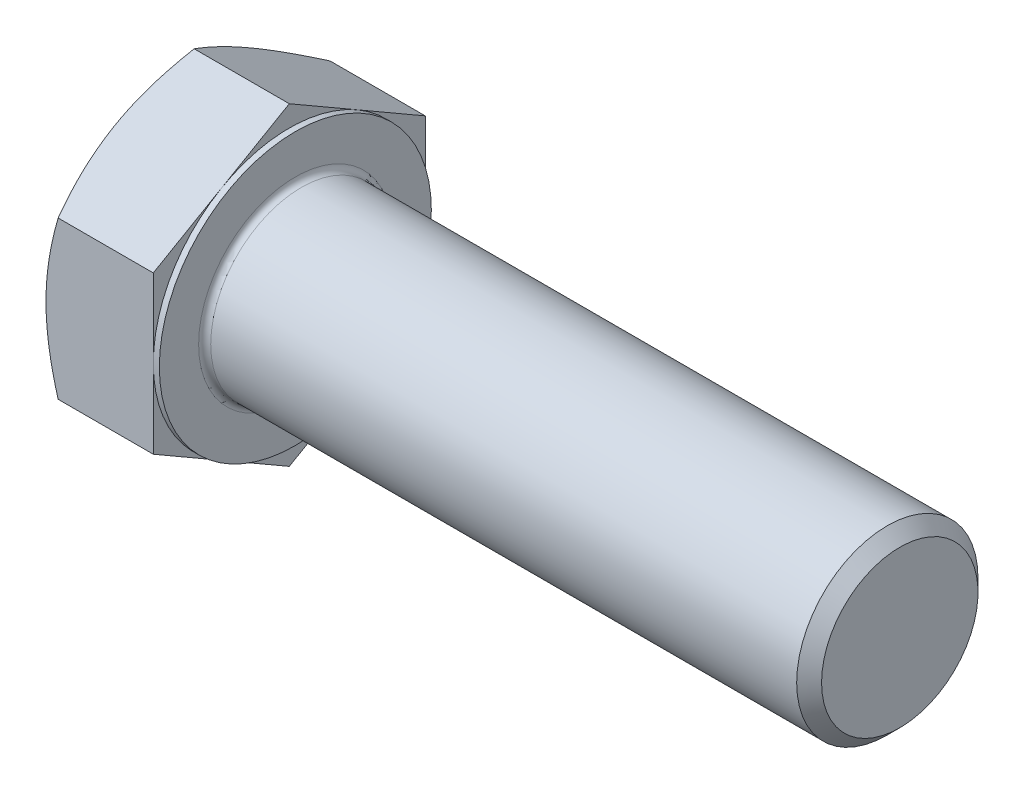
SolidWorks part; units mm, degrees
ref_plane "Front Plane" through (0, 0, 0) normal (0, 0, 1) x (1, 0, 0)
ref_plane "Top Plane" through (0, 0, 0) normal (0, 1, 0) x (1, 0, 0)
ref_plane "Right Plane" through (0, 0, 0) normal (1, 0, 0) x (0, 0, -1)
sketch "BaseHeadSke" plane through (0, 0, 0) normal (1, 0, 0) x (0, 0, -1)
  line L1 (18, 10.3923) -> (0, 20.7846)
  line L2 (0, 20.7846) -> (-18, 10.3923)
  line L3 (-18, 10.3923) -> (-18, -10.3923)
  line L4 (-18, -10.3923) -> (0, -20.7846)
  line L5 (0, -20.7846) -> (18, -10.3923)
  line L6 (18, -10.3923) -> (18, 10.3923)
  circle A0 centre (0, 0) radius 18 construction
extrude "BaseHead" add sketch "BaseHeadSke" along normal blind 15
sketch "BodySke" plane through (0, 0, 0) normal (0, 0, 1) x (1, 0, 0)
  line L0 (0, 0) -> (95, 0)
  line L1 (95, 0) -> (95, 10.352)
  line L2 (95, 10.352) -> (93.352, 12)
  line L3 (93.352, 12) -> (0, 12)
  line L4 (0, 12) -> (0, 0)
  line L5 (15, 10.3923) -> (15, -10.3923) construction
  line L6 (0, 0) -> (159.3976, 0) construction
  line L7 (15, -84.3176) -> (15, 77.7215) construction
  line L8 (92, -21.5941) -> (92, 39.2994) construction
  dimension "Thread_length" = 80
  dimension "Advance" = 3
revolve "BaseBody" add sketch "BodySke" angle 360 about L6
cosmetic thread "ThreadCosmetic" [suppressed] parameters "Thread_length"=80, "Thread_minor"=20.704
sketch "HeadChamferSke" plane through (0, 0, 0) normal (0, 0, 1) x (1, 0, 0)
  line L0 (1.6077, 20.7846) -> (0, 20.7846)
  line L1 (0, 20.7846) -> (0, 18)
  line L2 (0, 18) -> (1.6077, 20.7846)
  line L3 (0, 0) -> (120.9185, 0) construction
  dimension "D1" = 30
revolve "HeadChamfer" cut sketch "HeadChamferSke" angle 360 about L3
sketch "BearingFaceSke" plane through (0, 0, 0) normal (0, 0, 1) x (1, 0, 0)
  line L0 (0, 0) -> (129.6443, 0) construction
  line L1 (14.2, 20.7846) -> (15, 20.7846)
  line L2 (14.2, 20.7846) -> (14.2, 18)
  line L3 (14.2, 18) -> (15, 18)
  line L4 (15, 20.7846) -> (15, 18)
  dimension "D1" = 36
revolve "BearingFace" cut sketch "BearingFaceSke" angle 360 about L0
fillet "Fillet" radius 0.8 1 edges at (15, 0, 12)
sketch "ThdSchSke" plane through (0, 0, 0) normal (0, 0, 1) x (1, 0, 0)
  line L0 (91.0485, 13.9029) -> (91.0485, 12)
  line L1 (91.0485, 12) -> (92, 10.352)
  line L2 (92, 10.352) -> (92.9515, 12)
  line L3 (92.9515, 12) -> (92.9515, 13.9029)
  line L4 (92.9515, 13.9029) -> (91.0485, 13.9029)
  line L6 (0, 0) -> (141.9934, 0) construction
  line L7 (95, -10.352) -> (95, 10.352) construction
  dimension "D2" = 20.704
  dimension "D3" = 24
  dimension "Advance" = 3
revolve "ThreadSchematic" [suppressed] cut sketch "ThdSchSke" angle 360 about L6
pattern_linear "ThdSchPat" [suppressed] count 25 spacing 3 along (-1, 0, 0) of bodies 107
equation "\"Thread_minor@ThreadCosmetic\" = \"Minor_dia@BodySke\""
equation "\"Thread_length@ThreadCosmetic\" = \"Thread_length@BodySke\""
equation "\"Head_chamfer@HeadChamferSke\" = \"Width_flats@BaseHeadSke\""
equation "\"D1@BearingFaceSke\" = \"Width_flats@BaseHeadSke\""
equation "\"D2@ThdSchSke\" = \"Minor_dia@BodySke\""
equation "\"D3@ThdSchSke\" = \"Diameter@BodySke\""
equation "\"Advance@ThdSchSke\" = \"Advance@BodySke\""
equation "\"D3@ThdSchPat\" = \"Advance@BodySke\""
equation "\"D1@ThdSchPat\" =  int( \"Thread_length@BodySke\"/\"Advance@BodySke\" )-1"
